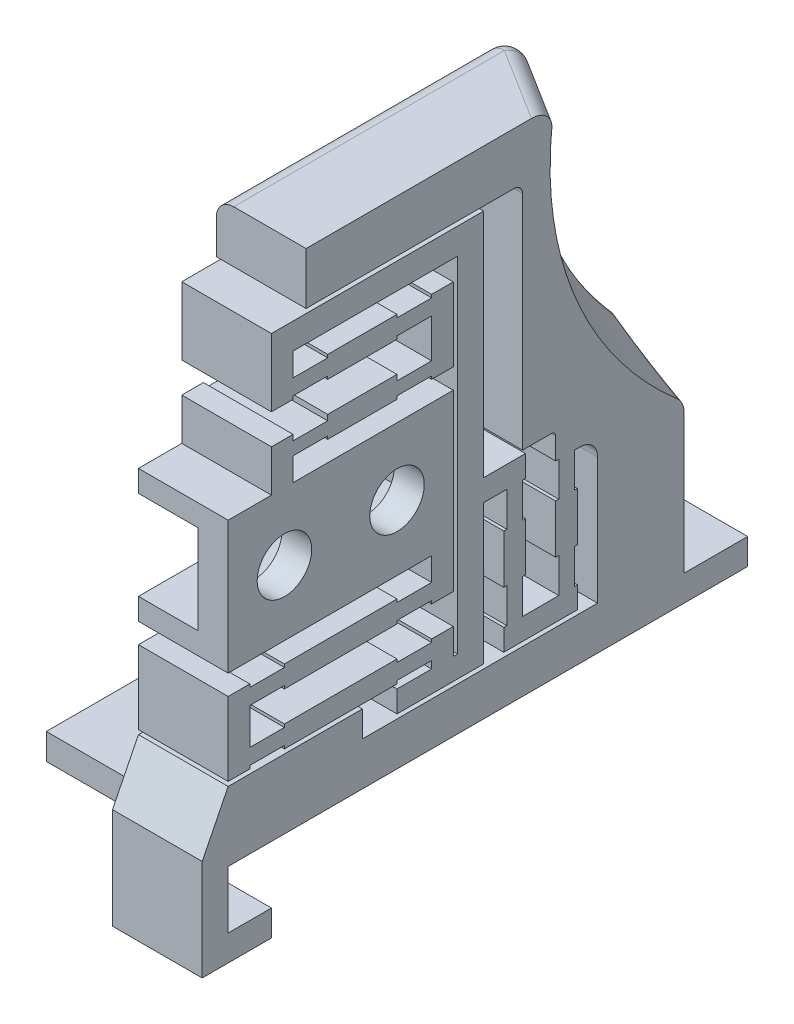
SolidWorks part; units mm, degrees
other "Markup1"
sketch "Sketch8" plane through (10.5, 0, 3) normal (0.7095, 0.0467, 0.7031) x (0.7044, -0.0184, -0.7096)
ref_plane "Front Plane" through (0, 0, 0) normal (0, 0, 1) x (1, 0, 0)
ref_plane "Top Plane" through (0, 0, 0) normal (0, 1, 0) x (1, 0, 0)
ref_plane "Right Plane" through (0, 0, 0) normal (1, 0, 0) x (0, 0, -1)
sketch "Sketch1" plane through (0, 0, 0) normal (1, 0, 0) x (0, 0, -1)
  line L0 (-0.75, -11.3333) -> (8.5, -11.3333)
  line L1 (8.5, -11.3333) -> (8.5, -21.4)
  line L2 (-4.5, -11.3333) -> (-4.5, -18.9833)
  line L3 (-4.5, -18.9833) -> (7.25, -18.9833)
  line L56 (7.25, -20.325) -> (5.25, -20.325)
  line L57 (-3.25, -21.225) -> (-3.25, -23.325)
  line L58 (-3.25, -23.325) -> (-1.25, -23.325)
  line L59 (8.5, -23.15) -> (8.5, -24.65)
  line L60 (7.25, -18.9833) -> (7.25, -20.325)
  line L61 (5.25, -20.325) -> (5.25, -20.15)
  line L62 (-4.5, -20.15) -> (-4.5, -24.4)
  line L63 (-1.25, -23.325) -> (-1.25, -23.15)
  line L64 (8.75, -4.75) -> (8.75, -24.65)
  line L65 (-0.75, -9.9917) -> (1.25, -9.9917)
  line L66 (7.25, -9.2417) -> (7.25, -6.9917)
  line L67 (7.25, -6.9917) -> (5.25, -6.9917)
  line L68 (-2, -7.1667) -> (-2, -3.25)
  line L69 (-0.75, -11.3333) -> (-0.75, -9.9917)
  line L70 (1.25, -9.9917) -> (1.25, -10.1667)
  line L71 (8.5, -10.1667) -> (8.5, -5.9167)
  line L72 (5.25, -6.9917) -> (5.25, -7.1667)
  line L73 (-0.75, -6.0917) -> (-0.75, -4.75)
  line L74 (-0.75, -4.75) -> (8.75, -4.75)
  line L75 (-2, -3.25) -> (10.25, -3.25)
  line L76 (1.25, -10.1667) -> (5.25, -10.1667)
  line L77 (5.25, -10.1667) -> (5.25, -9.9917)
  line L78 (5.25, -9.9917) -> (7.25, -9.9917)
  line L79 (7.25, -9.9917) -> (7.25, -10.1667)
  line L80 (7.25, -10.1667) -> (8.5, -10.1667)
  line L81 (7.25, -9.2417) -> (5.25, -9.2417)
  line L82 (5.25, -9.2417) -> (5.25, -8.9167)
  line L83 (5.25, -8.9167) -> (1.25, -8.9167)
  line L84 (1.25, -8.9167) -> (1.25, -9.2417)
  line L85 (1.25, -9.2417) -> (-0.75, -9.2417)
  line L86 (-0.75, -9.2417) -> (-0.75, -8.9167)
  line L87 (-0.75, -8.9167) -> (-2, -8.9167)
  line L88 (5.25, -7.1667) -> (1.25, -7.1667)
  line L89 (1.25, -7.1667) -> (1.25, -6.9917)
  line L90 (1.25, -6.9917) -> (-0.75, -6.9917)
  line L91 (-0.75, -6.9917) -> (-0.75, -7.1667)
  line L92 (-0.75, -7.1667) -> (-2, -7.1667)
  line L93 (-0.75, -6.0917) -> (1.25, -6.0917)
  line L94 (1.25, -6.0917) -> (1.25, -5.9167)
  line L95 (1.25, -5.9167) -> (5.25, -5.9167)
  line L96 (5.25, -5.9167) -> (5.25, -6.0917)
  line L97 (5.25, -6.0917) -> (7.25, -6.0917)
  line L98 (7.25, -6.0917) -> (7.25, -5.9167)
  line L99 (7.25, -5.9167) -> (8.5, -5.9167)
  line L100 (5.25, -20.15) -> (-1.25, -20.15)
  line L101 (-1.25, -20.15) -> (-1.25, -20.325)
  line L102 (-1.25, -20.325) -> (-3.25, -20.325)
  line L103 (-3.25, -20.325) -> (-3.25, -20.15)
  line L104 (-3.25, -20.15) -> (-4.5, -20.15)
  line L105 (8.5, -21.4) -> (7.25, -21.4)
  line L106 (7.25, -21.4) -> (7.25, -21.225)
  line L107 (7.25, -21.225) -> (5.25, -21.225)
  line L108 (5.25, -21.225) -> (5.25, -21.4)
  line L109 (5.25, -21.4) -> (-1.25, -21.4)
  line L110 (-1.25, -21.4) -> (-1.25, -21.225)
  line L111 (-1.25, -21.225) -> (-3.25, -21.225)
  line L112 (-1.25, -23.15) -> (5.25, -23.15)
  line L113 (5.25, -23.15) -> (5.25, -23.325)
  line L114 (5.25, -23.325) -> (7.25, -23.325)
  line L115 (7.25, -23.325) -> (7.25, -23.15)
  line L116 (7.25, -23.15) -> (8.5, -23.15)
  line L117 (-4.5, -24.4) -> (-3.25, -24.4)
  line L118 (-3.25, -24.4) -> (-3.25, -24.225)
  line L119 (-3.25, -24.225) -> (-1.25, -24.225)
  line L120 (-1.25, -24.225) -> (-1.25, -24.4)
  line L121 (-1.25, -24.4) -> (5.25, -24.4)
  line L122 (5.25, -24.4) -> (5.25, -24.225)
  line L123 (5.25, -24.225) -> (7.25, -24.225)
  line L124 (7.25, -24.225) -> (7.25, -24.65)
  line L125 (8.75, -24.65) -> (8.5, -24.65)
  line L126 (7.25, -24.65) -> (5.25, -24.65)
  line L127 (5.25, -24.65) -> (5.25, -25.9)
  line L128 (5.25, -25.9) -> (10.25, -25.9)
  line L130 (14.5917, -24.65) -> (12.4917, -24.65)
  line L131 (12.4917, -24.65) -> (12.4917, -22.65)
  line L132 (12.4917, -22.65) -> (12.6667, -22.65)
  line L133 (12.6667, -22.65) -> (12.6667, -19.8333)
  line L134 (12.6667, -19.8333) -> (12.4917, -19.8333)
  line L135 (12.4917, -19.8333) -> (12.4917, -17.8333)
  line L136 (12.4917, -17.8333) -> (12.6667, -17.8333)
  line L137 (14.5917, -17.8333) -> (14.5917, -19.8333)
  line L138 (14.5917, -19.8333) -> (14.4167, -19.8333)
  line L139 (14.4167, -19.8333) -> (14.4167, -22.65)
  line L140 (14.4167, -22.65) -> (14.5917, -22.65)
  line L141 (14.5917, -22.65) -> (14.5917, -24.65)
  line L145 (11.5917, -24.65) -> (11.4167, -24.65)
  line L146 (11.5917, -24.65) -> (11.5917, -22.65)
  line L147 (11.5917, -22.65) -> (11.4167, -22.65)
  line L148 (11.4167, -22.65) -> (11.4167, -19.8333)
  line L149 (11.4167, -19.8333) -> (11.5917, -19.8333)
  line L150 (11.5917, -17.8333) -> (10.25, -17.8333)
  line L151 (11.5917, -19.8333) -> (11.5917, -17.8333)
  line L153 (10.25, -16.5833) -> (12.6667, -16.5833)
  line L155 (15.8333, -17.8333) -> (15.4917, -17.8333)
  line L156 (15.4917, -17.8333) -> (15.4917, -19.8333)
  line L157 (15.4917, -19.8333) -> (15.6667, -19.8333)
  line L158 (15.6667, -19.8333) -> (15.6667, -22.65)
  line L159 (15.6667, -22.65) -> (15.4917, -22.65)
  line L160 (15.4917, -22.65) -> (15.4917, -24.65)
  line L168 (16.8333, -26.15) -> (16.8333, -18.8333)
  line L179 (16.8333, -26.15) -> (3.25, -26.15)
  line L180 (3.25, -26.15) -> (3.25, -24.65)
  line L181 (3.25, -24.65) -> (-4.5, -24.65)
  line L184 (-4.5, -28.65) -> (21.8333, -28.65)
  line L187 (21.8333, 0) -> (0, 0)
  line L189 (10.25, -25.9) -> (10.25, -17.8333)
  line L190 (12, -3) -> (0, -3)
  line L191 (0, -3) -> (0, 0)
  line L192 (15.6667, -24.65) -> (15.4917, -24.65)
  line L193 (14.1667, -16.3333) -> (12.5, -16.3333)
  line L194 (12.5, -16.3333) -> (12.5, -3.5)
  line L198 (11.4167, -24.65) -> (11.4167, -25.9)
  line L199 (15.6667, -24.65) -> (15.6667, -25.9)
  line L200 (15.6667, -25.9) -> (11.4167, -25.9)
  line L201 (10.25, -16.5833) -> (10.25, -3.25)
  line L203 (14.4167, -17.8333) -> (14.4167, -16.5833)
  line L204 (12.6667, -17.8333) -> (12.6667, -16.5833)
  line L205 (14.4167, -17.8333) -> (14.5917, -17.8333)
  line L208 (-4.5, -28.65) -> (-4.5, -31.98)
  line L209 (-4.5, -31.98) -> (-2, -31.98)
  line L210 (-2, -31.98) -> (-2, -33.48)
  line L211 (-2, -33.48) -> (-6, -33.48)
  line L212 (-6, -33.48) -> (-6, -27.65)
  line L213 (-6, -27.65) -> (-4.5, -24.65)
  line L214 (-2, -11.3333) -> (-4.5, -11.3333)
  line L215 (-2, -11.3333) -> (-2, -8.9167)
  line L216 (21.8333, 0) -> (21.8333, -28.65)
  arc A1 (12.5, -3.5) -> (12, -3) centre (12, -3.5) ccw
  arc A4 (15.8333, -17.8333) -> (16.8333, -18.8333) centre (15.8333, -18.8333) cw
  arc A5 (14.4167, -16.5833) -> (14.1667, -16.3333) centre (14.1667, -16.5833) ccw
  point P120 (12.5, -3)
  point P140 (16.8333, -17.8333)
  point P144 (14.4167, -16.3333)
  point P159 (-1.375, -7.1667)
  point P199 (15.4917, -23.65)
  dimension "D56" = 0.5
  dimension "D61" = 1
  dimension "D62" = 0.25
  dimension "D3" = 4.25
  dimension "D4" = 0.175
  dimension "D5" = 1.25
  dimension "D6" = 0.9
  dimension "D7" = 1.75
  dimension "D8" = 0.175
  dimension "D9" = 0.9
  dimension "D10" = 1.1667
  dimension "D11" = 0.25
  dimension "D13" = 4.25
  dimension "D14" = 1.1667
  dimension "D15" = 0.175
  dimension "D16" = 1.25
  dimension "D17" = 0.75
  dimension "D18" = 1.75
  dimension "D19" = 0.175
  dimension "D21" = 0.9
  dimension "D22" = 1.1667
  dimension "D23" = 1.5
  dimension "D24" = 0.25
  dimension "D25" = 0.25
  dimension "D34" = 2.5
  dimension "D35" = 2
  dimension "D36" = 2
  dimension "D37" = 1.25
  dimension "D38" = 1.25
  dimension "D40" = 0.25
  dimension "D41" = 1.25
  dimension "D42" = 1.1667
  dimension "D43" = 0.175
  dimension "D44" = 0.9
  dimension "D45" = 1.75
  dimension "D46" = 0.175
  dimension "D47" = 0.9
  dimension "D48" = 1.25
  dimension "D12" = 7.65
  dimension "D20" = 1.5
  dimension "D26" = 1.25
  dimension "D27" = 1.1667
  dimension "D28" = 0.25
  dimension "D32" = 2
  dimension "D33" = 1.25
  dimension "D49" = 2.25
  dimension "D50" = 0.25
  dimension "D39" = 13
  dimension "D30" = 2
  dimension "D53" = 1.5
  dimension "D57" = 1.5
  dimension "D58" = 3.33
  dimension "D59" = 4
  dimension "D31" = 3
  dimension "D54" = 5
  dimension "D55" = 1.25
  dimension "D60" = 1
  dimension "D63" = 2
  dimension "D65" = 2.5
  dimension "D64" = 2
  dimension "D51" = 5
  dimension "D29" = 2
extrude "Boss-Extrude1" add sketch "Sketch1" along normal blind 5.18
sketch "Sketch2" plane through (0, 0, 4.5) normal (0, 0, 1) x (1, 0, 0)
  line L0 (5.18, -11.3333) -> (5.18, -18.9833) construction
  line L1 (5.18, -17.7333) -> (1.73, -17.7333)
  line L2 (5.18, -17.7333) -> (5.18, -12.5833)
  line L3 (5.18, -12.5833) -> (1.73, -12.5833)
  line L4 (1.73, -17.7333) -> (1.73, -12.5833)
  line L5 (5.18, -11.3333) -> (5.18, -18.9833) construction
  dimension "D1" = 3.45
  dimension "D2" = 1.25
  dimension "D3" = 1.25
extrude "Cut-Extrude4" cut sketch "Sketch2" against normal up to next
sketch "Sketch3" plane through (0, -28.65, 0) normal (0, -1, 0) x (1, 0, 0)
  line L1 (0, -25.5) -> (10.5, -25.5)
  line L2 (0, -25.5) -> (0, 4.5)
  line L3 (0, 4.5) -> (10.5, 4.5)
  line L4 (10.5, -25.5) -> (10.5, 4.5)
  line L5 (5.18, 4.5) -> (5.18, -21.8333) construction
  line L8 (0, 4.5) -> (0, -21.8333) construction
  circle A0 centre (7.92, -10.73) radius 1.575
  circle A1 centre (7.92, -22.73) radius 1.575
  dimension "D3" = 3.15
  dimension "D1" = 10.5
  dimension "D2" = 2.74
  dimension "D4" = 12
  dimension "D5" = 30
  dimension "D6" = 15.23
sketch "Sketch7" plane through (0, 0, 0) normal (-1, 0, 0) x (0, 0, 1)
  line L0 (2, -11.3333) -> (4.5, -11.3333) construction
  line L1 (4.5, -11.3333) -> (4.5, -18.9833) construction
  circle A0 centre (1.25, -15.2083) radius 1.575
  circle A1 centre (-5.25, -15.2083) radius 1.575
  dimension "D1" = 3.15
  dimension "D2" = 3.875
  dimension "D3" = 3.25
  dimension "D4" = 6.5
extrude "Cut-Extrude3" cut sketch "Sketch7" against normal up to next
extrude "Boss-Extrude2" add sketch "Sketch3" against normal blind 1.5
mirror "Mirror1" [suppressed] of bodies 111
delete or keep bodies "Body-Delete/Keep 1" [suppressed] type delete bodies bodies 111
ref_plane "Plane1" through (5.5172, 0, -3.4556) normal (-0.8475, 0, 0.5308) x (0, -1, 0)
sketch "Sketch10" plane through (5.5172, 0, -3.4556) normal (-0.8475, 0, 0.5308) x (0, -1, 0)
  line L1 (28.65, 3.8137) -> (28.65, -21.6111) construction
  line L2 (28.65, 9.3872) -> (28.65, -36.5965) construction
  circle A0 centre (3, -33.6928) radius 21.75
  dimension "D2" = 43.5
  dimension "D1" = 43.08
  dimension "D3" = 25.65
extrude "Cut-Extrude5" cut sketch "Sketch10" against normal blind 25
fillet "Fillet1" radius 1 5 edges at (2.7415, -17.0009, -21.8333) (2.59, 0, -15.9594) (5.18, -21.2244, -21.8333) (5.18, -7.9863, -18.0198) (5.18, 0, -8.7908)
mirror "Mirror2" about plane through (0, -18.8333, -15.8333) normal (-1, 0, 0) of bodies 113
delete or keep bodies "Body-Delete/Keep 2" type delete bodies bodies 113
equation "\"VerticalFlexureWidth\"= 1.3"
equation "\"VerticalFlexureGap\"= 1"
equation "\"VerticalDoubleFlexureWidth\"= 2 * \"VerticalFlexureWidth\" + \"VerticalFlexureGap\""
equation "\"HorizontalFlexureLength\"= 7"
equation "\"FlexureJointWidth\"= 1.25"
equation "\"HeadHeight\"= 7.5"
equation "\"VerticalFlexureLength\"= 18"
equation "\"MinGap\"= 0.25"
equation "\"BaseplateHeight+Tolerance\"= 3.33"
equation "\"HeadWidth\"= 13"
equation "\"D1@Boss-Extrude1\"=5.18"
equation "\"HorizontalFlexureWidth\"= 1"
equation "\"HorizontalFlexureGap\"= 1"
equation "\"HorizontalDoubleFlexureWidth\"= 2 * \"HorizontalFlexureWidth\" + \"HorizontalFlexureGap\""
equation "\"FlexureWidth\"= 0.9"
equation "\"FlexureWideWidth\"=1.25"
equation "\"FlexureGap\"=1.75"
equation "\"TwinFlexureWidth\"= \"FlexureGap\" + 2 * \"FlexureWideWidth\""
equation "\"D3@Sketch1\"=\"TwinFlexureWidth\""
equation "\"FlexureNeckWidth\"= ( \"FlexureWideWidth\" - \"FlexureWidth\" ) / 2"
equation "\"D4@Sketch1\"=\"FlexureNeckWidth\""
equation "\"D5@Sketch1\"=\"FlexureWideWidth\""
equation "\"D6@Sketch1\"=\"FlexureWidth\""
equation "\"D7@Sketch1\"=\"FlexureGap\""
equation "\"D8@Sketch1\"=\"FlexureNeckWidth\""
equation "\"D9@Sketch1\"=\"FlexureWidth\""
equation "\"D10@Sketch1\"=\"FlexureGapEdge\""
equation "\"D11@Sketch1\"=\"MinGap\""
equation "\"D13@Sketch1\"=\"TwinFlexureWidth\""
equation "\"D14@Sketch1\"=\"FlexureGapEdge\""
equation "\"D15@Sketch1\"=\"FlexureNeckWidth\""
equation "\"D16@Sketch1\"=\"FlexureWideWidth\""
equation "\"D19@Sketch1\"=\"FlexureNeckWidth\""
equation "\"D21@Sketch1\"=\"FlexureWidth\""
equation "\"D18@Sketch1\"=\"FlexureGap\""
equation "\"D22@Sketch1\"=\"FlexureGapEdge\""
equation "\"FlexureLength\"= 2"
equation "\"MainSupport\"=1.5"
equation "\"D23@Sketch1\"=\"MainSupport\""
equation "\"D24@Sketch1\"=\"MinGap\""
equation "\"D25@Sketch1\"=\"MinGap\""
equation "\"D35@Sketch1\"=\"FlexureLength\""
equation "\"D36@Sketch1\"=\"FlexureLength\""
equation "\"D37@Sketch1\"=\"FlexureJointWidth\""
equation "\"D38@Sketch1\"=\"FlexureJointWidth\""
equation "\"D40@Sketch1\"=\"MinGap\""
equation "\"D41@Sketch1\"=\"FlexureWideWidth\""
equation "\"D42@Sketch1\"=\"FlexureGapEdge\""
equation "\"D43@Sketch1\"=\"FlexureNeckWidth\""
equation "\"D44@Sketch1\"=\"FlexureWidth\""
equation "\"D46@Sketch1\"=\"FlexureNeckWidth\""
equation "\"D47@Sketch1\"=\"FlexureWidth\""
equation "\"D48@Sketch1\"=\"FlexureWideWidth\""
equation "\"D20@Sketch1\"=\"MainSupport\""
equation "\"D26@Sketch1\"=\"FlexureJointWidth\""
equation "\"D27@Sketch1\"=\"FlexureGapEdge\""
equation "\"D28@Sketch1\"=\"MinGap\""
equation "\"D32@Sketch1\"=\"FlexureLength\""
equation "\"D33@Sketch1\"=\"FlexureJointWidth\""
equation "\"D30@Sketch1\"=\"FlexureLength\""
equation "\"D53@Sketch1\"=\"MainSupport\""
equation "\"D57@Sketch1\"=\"MainSupport\""
equation "\"D58@Sketch1\"=\"BaseplateHeight+Tolerance\""
equation "\"D39@Sketch1\"=\"HeadWidth\""
equation "\"FlexureGapEdge\"= \"FlexureGap\" * ( 2 / 3 )"
equation "\"D55@Sketch1\"=\"FlexureJointWidth\""
equation "\"D63@Sketch1\"=\"FlexureLength\""
equation "\"FlexurePlateConnectionHeigh\"= 5.15 + 2.5"
equation "\"D12@Sketch1\"=\"FlexurePlateConnectionHeigh\""
equation "\"D64@Sketch1\"=\"FlexureGap\"+0.25"
equation "\"D45@Sketch1\"=\"FlexureGap\""
